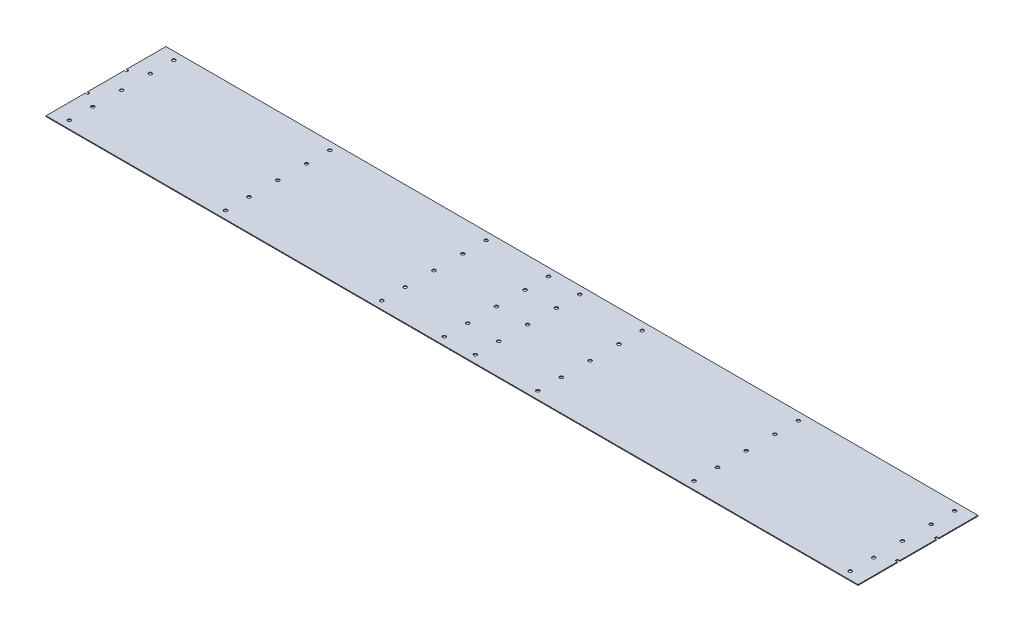
SolidWorks part; units mm, degrees
ref_plane "Front Plane" through (0, 0, 0) normal (0, 0, 1) x (1, 0, 0)
ref_plane "Top Plane" through (0, 0, 0) normal (0, 1, 0) x (1, 0, 0)
ref_plane "Right Plane" through (0, 0, 0) normal (1, 0, 0) x (0, 0, -1)
sketch "Sketch1" plane through (0, 0, 0) normal (0, 1, 0) x (1, 0, 0)
  line L0 (-20, -26.5) -> (-20, -76.8)
  line L1 (-20, -76.8) -> (1020, -76.8)
  line L2 (1020, -76.8) -> (1020, -26.5)
  line L3 (1020, -26.5) -> (-20, -26.5) construction
  line L4 (0, 0) -> (-17, 0) construction
  line L5 (-20, -26.5) -> (-17, -26.5)
  line L7 (-17, 26.5) -> (-20, 26.5)
  line L8 (-20, 26.5) -> (-20, 76.8)
  line L9 (-20, 76.8) -> (1020, 76.8)
  line L10 (1020, 76.8) -> (1020, 26.5)
  line L11 (1020, 26.5) -> (1017, 26.5)
  line L13 (1017, -26.5) -> (1020, -26.5)
  line L14 (0, 36.8) -> (480, 36.8) construction
  line L15 (-17, 26.5) -> (-17, 23.5)
  line L16 (-17, 26.5) -> (1017, 26.5) construction
  line L17 (1017, 26.5) -> (1017, -26.5) construction
  line L18 (-17, 26.5) -> (-17, -26.5) construction
  line L19 (-17, 23.5) -> (-20, 23.5)
  line L20 (-20, 23.5) -> (-20, -23.5)
  line L21 (-20, -23.5) -> (-17, -23.5)
  line L22 (-17, -23.5) -> (-17, -26.5)
  line L23 (1017, 26.5) -> (1017, 23.5)
  line L24 (1017, 23.5) -> (1020, 23.5)
  line L25 (1020, 23.5) -> (1020, -23.5)
  line L26 (1020, -23.5) -> (1017, -23.5)
  line L27 (1017, -23.5) -> (1017, -26.5)
  line L28 (1020, 0) -> (1017, 0) construction
  line L29 (480, 36.8) -> (480, -36.8) construction
  line L30 (-17, 0) -> (-20, 0) construction
  line L31 (0, 36.8) -> (0, -36.8) construction
  line L32 (480, -36.8) -> (0, -36.8) construction
  line L33 (0, 36.8) -> (0, 66.8) construction
  line L34 (0, 66.8) -> (480, 66.8) construction
  line L35 (480, 66.8) -> (480, 36.8) construction
  line L36 (480, -36.8) -> (480, -66.8) construction
  line L37 (480, -66.8) -> (0, -66.8) construction
  line L38 (0, -66.8) -> (0, -36.8) construction
  line L39 (0, 0) -> (480, 0) construction
  line L40 (200, 66.8) -> (200, 36.8) construction
  line L41 (200, 36.8) -> (200, 0) construction
  line L42 (200, 0) -> (200, -36.8) construction
  line L43 (200, -36.8) -> (200, -66.8) construction
  line L44 (500, 76.8) -> (500, -76.8) construction
  line L45 (480, 66.8) -> (500, 66.8) construction
  line L46 (500, 66.8) -> (520, 66.8) construction
  line L47 (520, 66.8) -> (520, -66.8) construction
  line L48 (520, -66.8) -> (480, -66.8) construction
  line L49 (480, -36.8) -> (520, -36.8) construction
  line L50 (400, 66.8) -> (400, -66.8) construction
  line L51 (480, 0) -> (520, 0) construction
  line L53 (480, 36.8) -> (520, 36.8) construction
  line L54 (600, 66.8) -> (600, -66.8) construction
  line L56 (800, 66.8) -> (800, -66.8) construction
  line L58 (1000, 66.8) -> (1000, -66.8) construction
  circle A0 centre (0, -36.8) radius 2.15
  circle A30 centre (0, 36.8) radius 2.15
  circle A31 centre (0, -66.8) radius 2.15
  circle A32 centre (0, 66.8) radius 2.15
  circle A33 centre (200, -66.8) radius 2.15
  circle A34 centre (200, -36.8) radius 2.15
  circle A35 centre (200, 36.8) radius 2.15
  circle A36 centre (200, 66.8) radius 2.15
  circle A53 centre (0, 0) radius 2.15
  circle A54 centre (480, 0) radius 2.15
  circle A55 centre (200, 0) radius 2.15
  circle A59 centre (480, 66.8) radius 2.15
  circle A60 centre (480, 36.8) radius 2.15
  circle A61 centre (480, -36.8) radius 2.15
  circle A62 centre (480, -66.8) radius 2.15
  circle A63 centre (400, -66.8) radius 2.15
  circle A64 centre (400, -36.8) radius 2.15
  circle A65 centre (400, 36.8) radius 2.15
  circle A66 centre (400, 66.8) radius 2.15
  circle A67 centre (600, -66.8) radius 2.15
  circle A68 centre (600, -36.8) radius 2.15
  circle A69 centre (600, 36.8) radius 2.15
  circle A70 centre (600, 66.8) radius 2.15
  circle A71 centre (800, -66.8) radius 2.15
  circle A72 centre (800, -36.8) radius 2.15
  circle A73 centre (800, 36.8) radius 2.15
  circle A74 centre (800, 66.8) radius 2.15
  circle A75 centre (1000, -66.8) radius 2.15
  circle A76 centre (1000, -36.8) radius 2.15
  circle A77 centre (1000, 36.8) radius 2.15
  circle A78 centre (1000, 66.8) radius 2.15
  circle A79 centre (520, -66.8) radius 2.15
  circle A80 centre (520, -36.8) radius 2.15
  circle A81 centre (520, 0) radius 2.15
  circle A82 centre (520, 36.8) radius 2.15
  circle A83 centre (520, 66.8) radius 2.15
  circle A84 centre (600, 0) radius 2.15
  circle A85 centre (800, 0) radius 2.15
  circle A86 centre (1000, 0) radius 2.15
  circle A87 centre (400, 0) radius 2.15
  point P2 (-18.5, 23.5)
  point P17 (0, 51.8)
  dimension "D12" = 4.3
  dimension "D8" = 3
  dimension "D1" = 3
  dimension "D6" = 30
  dimension "D7" = 10
  dimension "D4" = 20
  dimension "D15" = 200
  dimension "D3" = 13.3
  dimension "D11" = 13.3
  dimension "D2" = 47
  dimension "D5" = 20
  dimension "D10" = 40
  dimension "D9" = 6
  dimension "D14" = 2
extrude "Boss-Extrude1" add sketch "Sketch1" along normal blind 1 contours L27 L26 L25 L24 L23 L11 L10 L9 L8 L7 L15 L19 L20 L21 L22 L5 L0 L1 L2 L13 A54 A53 A36 A35 A34 A33 A32 A31 A30 A0 region at (500, 0, 0)
equation "\"skin_sheetmetal_thickness\"= 0.80"
equation "\"base_width_skin_spacer\" = \"base_width_skin_target_width\" - 4 * \"skin_sheetmetal_thickness\" - 2 * \"base_width_skin_target_bend_radius\""
equation "\"base_width_skin_inner\" = \"base_width_skin_spacer\" + 2 * \"skin_sheetmetal_thickness\""
equation "\"base_width_skin_outer\" = \"base_width_skin_inner\" + 2 * \"skin_sheetmetal_thickness\""
equation "\"bend_cut_width\"= 3"
equation "\"bend_cut_length\"= 3"
equation "\"bend_offset_inner\"= 12.5"
equation "\"bend_offset_outer\" = \"bend_offset_inner\" + \"skin_sheetmetal_thickness\""
equation "\"border_offset_ends\"= 20"
equation "\"border_offset_sides\"= 10"
equation "\"border_offset_flange_horiz\"= 10"
equation "\"rivet_size\"= 4.3"
equation "\"rivet_offset_ends\"= \"rivet_spacing_horiz\"/2 - \"border_offset_ends\""
equation "\"rivet_spacing_horiz\"= 200"
equation "\"rivet_spacing_vert\"= 30"
equation "\"rivet_spacing_offset_right\"= 40"
equation "\"base_length\"= 200"
equation "\"base_width_skin_spacer_length\" = 315"
equation "\"bend_offset_spacer_tab\"= 21.0"
equation "\"D6@Sketch1\"=\"rivet_spacing_vert\""
equation "\"D3@Sketch1\"=\"bend_offset_outer\""
equation "\"D1@Sketch1\"=\"bend_cut_length\""
equation "\"D8@Sketch1\"=\"bend_cut_width\""
equation "\"D2@Sketch1\"=\"base_width_skin_outer\""
equation "\"D4@Sketch1\"=\"border_offset_ends\""
equation "\"D7@Sketch1\"=\"border_offset_flange_horiz\""
equation "\"D12@Sketch1\"=\"rivet_size\""
equation "\"D15@Sketch1\"=\"rivet_spacing_horiz\""
equation "\"D5@Sketch1\"=\"border_offset_ends\""
equation "\"D10@Sketch1\"=\"rivet_spacing_offset_right\""
equation "\"base_width_skin_target_width\" = 50"
equation "\"base_width_skin_target_bend_radius\" = 1.5"
